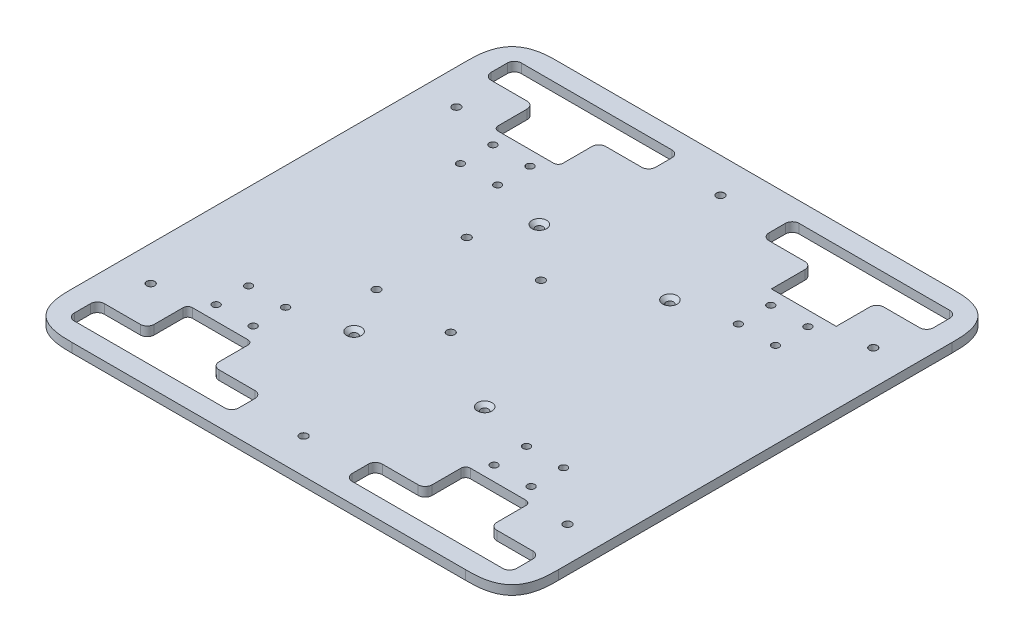
SolidWorks part; units mm, degrees
ref_plane "Спереди" through (0, 0, 0) normal (0, 0, 1) x (1, 0, 0)
ref_plane "Сверху" through (0, 0, 0) normal (0, 1, 0) x (1, 0, 0)
ref_plane "Справа" through (0, 0, 0) normal (1, 0, 0) x (0, 0, -1)
sketch "Эскиз1" plane through (0, 0, 0) normal (0, 1, 0) x (1, 0, 0)
  line L1 (-150, -150) -> (150, -150) construction
  line L2 (-150, -150) -> (-150, 150) construction
  line L3 (-150, 150) -> (150, 150) construction
  line L4 (150, -150) -> (150, 150) construction
  line L5 (-150, -150) -> (150, 150) construction
  line L6 (-150, 150) -> (150, -150) construction
  line L7 (-105, -105) -> (105, -105)
  line L8 (-105, -105) -> (-105, 105)
  line L9 (-105, 105) -> (105, 105)
  line L10 (105, -105) -> (105, 105)
  line L11 (-105, -105) -> (105, 105) construction
  line L12 (-105, 105) -> (105, -105) construction
  circle A0 centre (0, 0) radius 150 construction
  point P0 (0, 0)
  point P6 (0, 0)
  dimension "D1" = 300
  dimension "D2" = 210
extrude "Бобышка-Вытянуть1" add sketch "Эскиз1" along normal blind 4 contours L8 L9 L10 L7
fillet "Скругление1" radius 20 4 edges at (-105, 2, -105) (105, 2, -105) (105, 2, 105) (-105, 2, 105) curvature continuous yes
hole_wizard "Сверло под метчик  спиральное M31" positions "Эскиз33" profile "Эскиз34" hole size "M3x0.5" standard "DIN"
sketch "Эскиз33" plane through (0, 4, 0) normal (0, 1, 0) x (1, 0, 0)
  point P0 (-68, 59.75)
  point P3 (-52, 59.75)
  point P6 (-68, 45.75)
  point P9 (-52, 45.75)
  point P12 (-52, -59.75)
  point P15 (-52, -45.75)
  point P20 (-68, -59.75)
  point P23 (52, -59.75)
  point P26 (52, -45.75)
  point P29 (68, -59.75)
  point P32 (68, -45.75)
  point P35 (52, 59.75)
  point P42 (52, 45.75)
  point P45 (-68, -45.75)
  point P48 (68, 45.75)
  point P51 (68, 59.75)
sketch "Эскиз34" plane through (-68, 4, -59.75) normal (1, 0, 0) x (0, 0, 1)
  line L0 (0, 0) -> (0, 8.9464)
  line L1 (0, 8.9464) -> (1.575, 8)
  line L2 (1.575, 8) -> (1.575, 0)
  line L5 (1.575, 0) -> (0, 0)
  line L10 (0, 8.9464) -> (-1.575, 8) construction
  line L11 (0, -6.35) -> (0, 107.95) construction
  dimension "Диаметр отверстия" = 3.15
  dimension "Глубина отверстия" = 8
  dimension "Угол заточки сверла" = 118
hole_wizard "Отверстие с зазором M35" positions "Эскиз39" profile "Эскиз40" hole size "M3" standard "DIN" end condition through all
sketch "Эскиз39" plane through (0, 4, 0) normal (0, 1, 0) x (1, 0, 0)
  point P0 (90, 66)
  point P3 (-90, 66)
  point P6 (-90, -66)
  point P9 (90, -66)
  point P12 (0, -90)
  point P15 (0, 90)
sketch "Эскиз40" plane through (90, 4, -66) normal (1, 0, 0) x (0, 0, 1)
  line L0 (0, 0) -> (0, 4.05)
  line L1 (0, 4.05) -> (1.7, 4.05)
  line L2 (1.7, 4.05) -> (1.7, 0.025)
  line L3 (1.7, 0.025) -> (1.725, 0)
  line L5 (1.725, 0) -> (0, 0)
  line L6 (-1.7, 0.025) -> (-1.725, 0) construction
  line L11 (0, -6.35) -> (0, 107.95) construction
  dimension "Диаметр сквозного отверстия" = 3.4
  dimension "Глубина сквозного отверстия" = 4.05
  dimension "Диаметр передней зенковки" = 3.45
  dimension "Угол передней зенковки" = 90
hole_wizard "Зенковка для винта с полупотайной головкой M31" positions "Эскиз43" profile "Эскиз44" countersink size "M3" standard "DIN"
sketch "Эскиз43" plane through (0, 4, 0) normal (0, 1, 0) x (1, 0, 0)
  arc A0 (28.2, 41.55) -> (28.2, 38.45) centre (28.2, 40) ccw construction
  arc A1 (28.2, 38.45) -> (28.2, 41.55) centre (28.2, 40) ccw construction
  arc A2 (-28.2, 38.45) -> (-28.2, 41.55) centre (-28.2, 40) ccw construction
  arc A3 (-28.2, 41.55) -> (-28.2, 38.45) centre (-28.2, 40) ccw construction
  arc A4 (28.2, 41.55) -> (28.2, 38.45) centre (28.2, 40) ccw construction
  arc A5 (28.2, 38.45) -> (28.2, 41.55) centre (28.2, 40) ccw construction
  arc A6 (-28.2, 38.45) -> (-28.2, 41.55) centre (-28.2, 40) ccw construction
  arc A7 (-28.2, 41.55) -> (-28.2, 38.45) centre (-28.2, 40) ccw construction
  arc A8 (-28.2, -41.55) -> (-28.2, -38.45) centre (-28.2, -40) ccw construction
  arc A9 (-28.2, -38.45) -> (-28.2, -41.55) centre (-28.2, -40) ccw construction
  arc A10 (28.2, -41.55) -> (28.2, -38.45) centre (28.2, -40) ccw construction
  arc A11 (28.2, -38.45) -> (28.2, -41.55) centre (28.2, -40) ccw construction
  arc A12 (-28.2, -41.55) -> (-28.2, -38.45) centre (-28.2, -40) ccw construction
  arc A13 (-28.2, -38.45) -> (-28.2, -41.55) centre (-28.2, -40) ccw construction
  arc A14 (28.2, -41.55) -> (28.2, -38.45) centre (28.2, -40) ccw construction
  arc A15 (28.2, -38.45) -> (28.2, -41.55) centre (28.2, -40) ccw construction
  point P1 (28.2, 40)
  point P7 (-28.2, 40)
  point P19 (-28.2, -40)
  point P25 (28.2, -40)
sketch "Эскиз44" plane through (28.2, 4, -40) normal (1, 0, 0) x (0, 0, 1)
  line L0 (0, 0) -> (0, 4.9614)
  line L1 (0, 4.9614) -> (1.6, 4)
  line L2 (1.6, 4) -> (1.6, 1.55)
  line L3 (1.6, 1.55) -> (3.15, 0)
  line L5 (3.15, 0) -> (0, 0)
  line L6 (-1.6, 1.55) -> (-3.15, 0) construction
  line L10 (0, 4.9614) -> (-1.6, 4) construction
  line L11 (0, -6.35) -> (0, 107.95) construction
  dimension "Диаметр отверстия" = 3.2
  dimension "Глубина отверстия" = 4
  dimension "Диаметр передней зенковки" = 6.3
  dimension "Угол передней зенковки" = 90
  dimension "Угол заточки сверла" = 118
sketch "Эскиз45" plane through (0, 4, 0) normal (0, 1, 0) x (1, 0, 0)
  line L0 (-140.0063, 0) -> (140.0063, 0) construction
  line L1 (-95.5, 96.5) -> (-24.5, 96.5)
  line L2 (-95.5, 96.5) -> (-95.5, 83.5)
  line L3 (-95.5, 83.5) -> (-24.5, 83.5)
  line L4 (-27.5, 95) -> (-92.5, 95) construction
  line L5 (-92.5, 85) -> (-27.5, 85) construction
  line L8 (-24.5, 96.5) -> (-24.5, 83.5)
  line L9 (-95.5, -96.5) -> (-95.5, -83.5)
  line L10 (-95.5, -96.5) -> (-24.5, -96.5)
  line L11 (-24.5, -96.5) -> (-24.5, -83.5)
  line L12 (-27.5, 95) -> (-92.5, 95)
  line L13 (-92.5, 85) -> (-27.5, 85)
  line L16 (-95.5, -83.5) -> (-24.5, -83.5)
  line L17 (0, -140.0063) -> (0, 140.0063) construction
  line L18 (24.5, -96.5) -> (24.5, -83.5)
  line L19 (95.5, -96.5) -> (95.5, -83.5)
  line L20 (95.5, -83.5) -> (24.5, -83.5)
  line L21 (95.5, -96.5) -> (24.5, -96.5)
  line L22 (95.5, 96.5) -> (95.5, 83.5)
  line L23 (24.5, 96.5) -> (24.5, 83.5)
  line L24 (95.5, 96.5) -> (24.5, 96.5)
  line L25 (95.5, 83.5) -> (24.5, 83.5)
  dimension "D1" = 1.5
  dimension "D2" = 1.5
  dimension "D3" = 3
  dimension "D4" = 3
extrude "Вырез-Вытянуть3" cut sketch "Эскиз45" against normal through all contours L8 L1 L2 L3 | L25 L22 L24 L23 | L21 L19 L20 L18 | L16 L9 L10 L11 region at (-60, 4, -90) region at (-60, 4, 90) region at (60, 4, 90) region at (60, 4, -90)
sketch "Эскиз17" plane through (0, 4, 0) normal (0, 1, 0) x (1, 0, 0)
  line L0 (-47, 69) -> (-73, 69) construction
  line L1 (-47, 67) -> (-73, 67) construction
  line L2 (-47, 69) -> (-73, 69) construction
  line L3 (-47, 67) -> (-73, 67) construction
  line L4 (-74, 83.5) -> (-46, 83.5)
  line L5 (-73, 67) -> (-47, 67) construction
  line L6 (-73, 67) -> (-73, 69) construction
  line L7 (-73, 69) -> (-47, 69) construction
  line L8 (-47, 67) -> (-47, 69) construction
  line L9 (-73, 67) -> (-47, 69) construction
  line L10 (-73, 69) -> (-47, 67) construction
  line L11 (-74, 70) -> (-46, 70)
  line L12 (-46, 66) -> (-46, 70)
  line L13 (-74, 66) -> (-46, 66)
  line L14 (-74, 66) -> (-74, 70)
  line L19 (-95.5, 83.5) -> (-24.5, 83.5) construction
  line L20 (0, -140.0063) -> (0, 140.0063) construction
  line L29 (-95.5, 83.5) -> (-24.5, 83.5) construction
  line L30 (-74, 70) -> (-74, 83.5)
  line L31 (-46, 70) -> (-46, 83.5)
  line L32 (46, 70) -> (46, 83.5)
  line L33 (46, 66) -> (46, 70)
  line L34 (74, 66) -> (46, 66)
  line L35 (74, 66) -> (74, 70)
  line L36 (74, 70) -> (74, 83.5)
  line L37 (74, 83.5) -> (46, 83.5)
  line L38 (-140.0063, 0) -> (140.0063, 0) construction
  line L39 (-46, -70) -> (-46, -83.5)
  line L40 (-46, -66) -> (-46, -70)
  line L41 (-74, -66) -> (-46, -66)
  line L42 (-74, -66) -> (-74, -70)
  line L43 (-74, -70) -> (-74, -83.5)
  line L44 (-74, -83.5) -> (-46, -83.5)
  line L45 (74, -83.5) -> (46, -83.5)
  line L46 (74, -70) -> (74, -83.5)
  line L47 (74, -66) -> (74, -70)
  line L48 (74, -66) -> (46, -66)
  line L49 (46, -66) -> (46, -70)
  line L50 (46, -70) -> (46, -83.5)
  point P4 (-60, 68)
  line M79 (-24.5, 83.5) -> (-95.5, 83.5)
  dimension "D1" = 1
extrude "Вырез-Вытянуть2" cut sketch "Эскиз17" against normal up to next contours L11 L31 L30 M79 | L14 L13 L12 L11 | L39 L44 L43 L42 L41 L40 | L45 L50 L49 L48 L47 L46 | L32 L37 L36 L35 L34 L33 region at (-60, 4, -76.75) region at (-60, 4, -68)
fillet "Скругление2" radius 2 6 edges at (-74, 2, -66) (-46, 2, -66) (46, 2, 66) (74, 2, 66) (-46, 2, 66) (-74, 2, 66)
fillet "Скругление3" radius 3 8 edges at (-46, 2, -83.5) (-74, 2, -83.5) (74, 2, 83.5) (46, 2, 83.5) (-46, 2, 83.5) (-74, 2, 83.5) (46, 2, -83.5) (74, 2, -83.5)
fillet "Скругление5" radius 3 16 edges at (-24.5, 2, -96.5) (-24.5, 2, -83.5) (-24.5, 2, 96.5) (-24.5, 2, 83.5) (-95.5, 2, 96.5) (-95.5, 2, 83.5) (-95.5, 2, -96.5) (-95.5, 2, -83.5) (24.5, 2, -83.5) (24.5, 2, -96.5) (95.5, 2, -96.5) (95.5, 2, -83.5) (95.5, 2, 83.5) (95.5, 2, 96.5) (24.5, 2, 96.5) (24.5, 2, 83.5)
hole_wizard "Зенковка для винта с полупотайной головкой M32" positions "Эскиз48" profile "Эскиз49" countersink size "M3" standard "DIN" end condition through all
sketch "Эскиз48" plane through (0, 0, 0) normal (0, -1, 0) x (-1, 0, 0)
  point P0 (39.0194, 19.4666)
  point P3 (6.9806, 19.4666)
  point P6 (6.9806, -19.4666)
  point P9 (39.0194, -19.4666)
sketch "Эскиз49" plane through (-39.0194, 0, -19.4666) normal (1, 0, 0) x (0, 0, -1)
  line L0 (0, 0) -> (0, 4.05)
  line L1 (0, 4.05) -> (1.7, 4.05)
  line L2 (1.7, 4.05) -> (1.7, 1.45)
  line L3 (1.7, 1.45) -> (3.15, 0)
  line L5 (3.15, 0) -> (0, 0)
  line L6 (-1.7, 1.45) -> (-3.15, 0) construction
  line L11 (0, -6.35) -> (0, 107.95) construction
  dimension "Диаметр сквозного отверстия" = 3.4
  dimension "Глубина сквозного отверстия" = 4.05
  dimension "Диаметр передней зенковки" = 6.3
  dimension "Угол передней зенковки" = 90
